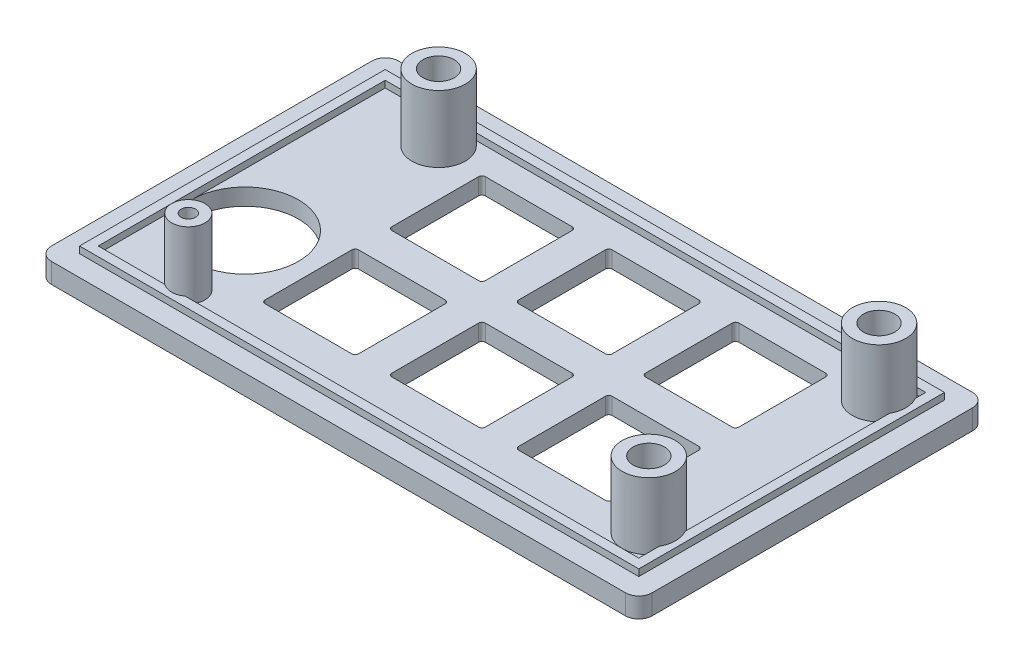
SolidWorks part; units mm, degrees
ref_plane "Front Plane" through (0, 0, 0) normal (0, 0, 1) x (1, 0, 0)
ref_plane "Top Plane" through (0, 0, 0) normal (0, 1, 0) x (1, 0, 0)
ref_plane "Right Plane" through (0, 0, 0) normal (1, 0, 0) x (0, 0, -1)
sketch "Sketch3" plane through (0, 0, 0) normal (0, 1, 0) x (1, 0, 0)
  line L0 (-45, 26) -> (45, 26)
  line L1 (-45, 26) -> (-45, -26)
  line L2 (-45, -26) -> (45, -26)
  line L3 (45, 26) -> (45, -26)
  dimension "D1" = 90
  dimension "D2" = 52
  dimension "D3" = 45
  dimension "D4" = 26
extrude "Boss-Extrude2" add sketch "Sketch3" along normal blind 3
fillet "Fillet2" radius 2 4 edges at (-45, 1.5, 26) (45, 1.5, 26) (45, 1.5, -26) (-45, 1.5, -26)
sketch "Sketch4" plane through (0, 0, 0) normal (0, 1, 0) x (1, 0, 0)
  line L1 (-41.5, 22.5) -> (41.5, 22.5)
  line L2 (-41.5, 22.5) -> (-41.5, -22.5)
  line L3 (-41.5, -22.5) -> (41.5, -22.5)
  line L4 (41.5, 22.5) -> (41.5, -22.5)
  dimension "D1" = 83
  dimension "D2" = 45
  dimension "D3" = 41.5
  dimension "D4" = 22.5
sketch "Sketch5" plane through (0, 0, 0) normal (0, 1, 0) x (1, 0, 0)
  line L8 (16.5, 17.5) -> (29.5, 17.5)
  line L9 (16.5, 3.5) -> (29.5, 3.5)
  line L10 (16, 17) -> (16, 4)
  line L11 (30, 17) -> (30, 4)
  line L25 (41.5, 22.5) -> (41.5, -22.5) construction
  line L26 (-2.5, 17.5) -> (10.5, 17.5)
  line L27 (-2.5, 3.5) -> (10.5, 3.5)
  line L28 (-3, 17) -> (-3, 4)
  line L29 (11, 17) -> (11, 4)
  line L30 (-21.5, 17.5) -> (-8.5, 17.5)
  line L31 (-21.5, 3.5) -> (-8.5, 3.5)
  line L32 (-22, 17) -> (-22, 4)
  line L33 (-8, 17) -> (-8, 4)
  line L34 (16.5, -1.5) -> (29.5, -1.5)
  line L35 (16.5, -15.5) -> (29.5, -15.5)
  line L36 (16, -2) -> (16, -15)
  line L37 (30, -2) -> (30, -15)
  line L38 (-2.5, -1.5) -> (10.5, -1.5)
  line L39 (-2.5, -15.5) -> (10.5, -15.5)
  line L40 (-3, -2) -> (-3, -15)
  line L41 (11, -2) -> (11, -15)
  line L42 (-21.5, -1.5) -> (-8.5, -1.5)
  line L43 (-21.5, -15.5) -> (-8.5, -15.5)
  line L44 (-22, -2) -> (-22, -15)
  line L45 (-8, -2) -> (-8, -15)
  line L46 (-41.5, 22.5) -> (-41.5, -22.5) construction
  line L47 (-41.5, -22.5) -> (41.5, -22.5) construction
  line L48 (-41.5, 22.5) -> (41.5, 22.5) construction
  arc A8 (16.5, 17.5) -> (16, 17) centre (16.5, 17) ccw
  arc A9 (30, 17) -> (29.5, 17.5) centre (29.5, 17) ccw
  arc A10 (16, 4) -> (16.5, 3.5) centre (16.5, 4) ccw
  arc A11 (29.5, 3.5) -> (30, 4) centre (29.5, 4) ccw
  arc A12 (-2.5, 17.5) -> (-3, 17) centre (-2.5, 17) ccw
  arc A13 (11, 17) -> (10.5, 17.5) centre (10.5, 17) ccw
  arc A14 (-3, 4) -> (-2.5, 3.5) centre (-2.5, 4) ccw
  arc A15 (10.5, 3.5) -> (11, 4) centre (10.5, 4) ccw
  arc A16 (-21.5, 17.5) -> (-22, 17) centre (-21.5, 17) ccw
  arc A17 (-8, 17) -> (-8.5, 17.5) centre (-8.5, 17) ccw
  arc A18 (-22, 4) -> (-21.5, 3.5) centre (-21.5, 4) ccw
  arc A19 (-8.5, 3.5) -> (-8, 4) centre (-8.5, 4) ccw
  arc A20 (16.5, -1.5) -> (16, -2) centre (16.5, -2) ccw
  arc A21 (30, -2) -> (29.5, -1.5) centre (29.5, -2) ccw
  arc A22 (16, -15) -> (16.5, -15.5) centre (16.5, -15) ccw
  arc A23 (29.5, -15.5) -> (30, -15) centre (29.5, -15) ccw
  arc A24 (-2.5, -1.5) -> (-3, -2) centre (-2.5, -2) ccw
  arc A25 (11, -2) -> (10.5, -1.5) centre (10.5, -2) ccw
  arc A26 (-3, -15) -> (-2.5, -15.5) centre (-2.5, -15) ccw
  arc A27 (10.5, -15.5) -> (11, -15) centre (10.5, -15) ccw
  arc A28 (-21.5, -1.5) -> (-22, -2) centre (-21.5, -2) ccw
  arc A29 (-8, -2) -> (-8.5, -1.5) centre (-8.5, -2) ccw
  arc A30 (-22, -15) -> (-21.5, -15.5) centre (-21.5, -15) ccw
  arc A31 (-8.5, -15.5) -> (-8, -15) centre (-8.5, -15) ccw
  circle A32 centre (-32.5, -7.5) radius 8
  dimension "D3" = 0.5
  dimension "D12" = 2
  dimension "D11" = 5
  dimension "D16" = 9
  dimension "D14" = 16
  dimension "D1" = 13
  dimension "D2" = 13
  dimension "D4" = 5
  dimension "D5" = 11.5
  dimension "D6" = 0.5
  dimension "D7" = 0.5
  dimension "D8" = 0.5
  dimension "D9" = 0.5
  dimension "D10" = 3
  dimension "D13" = 5
  dimension "D15" = 15
extrude "Cut-Extrude1" cut sketch "Sketch5" along normal through all both and the other way through all
sketch "Sketch7" plane through (0, 0, 0) normal (0, 1, 0) x (1, 0, 0)
  line L0 (-41.5, 22.5) -> (41.5, 22.5) construction
  line L1 (-41.5, 22.5) -> (-41.5, -22.5) construction
  line L2 (41.5, 22.5) -> (41.5, -22.5) construction
  line L3 (-41.5, -22.5) -> (41.5, -22.5) construction
  circle A0 centre (37, 18) radius 4
  circle A1 centre (-29, 18) radius 4
  circle A3 centre (37, -16.5) radius 4
  dimension "D1" = 8
  dimension "D2" = 4.5
  dimension "D3" = 12.5
  dimension "D4" = 4.5
  dimension "D5" = 6
extrude "Boss-Extrude3" add sketch "Sketch7" along normal blind 10 from surface starting at face at (23, 3, 8.5)
sketch "Sketch8" plane through (0, 0, 0) normal (0, 1, 0) x (1, 0, 0)
  circle A0 centre (-29, 18) radius 2.35
  circle A1 centre (37, 18) radius 2.35
  circle A2 centre (37, -16.5) radius 2.35
  dimension "D1" = 4.7
extrude "Cut-Extrude2" cut sketch "Sketch8" against normal blind 4 and the other way through all from surface starting at face at (-29, 13, -14)
sketch "Sketch10" plane through (0, 0, 0) normal (0, 1, 0) x (1, 0, 0)
  line L4 (40.5, 21.5) -> (-40.5, 21.5)
  line L5 (-40.5, 21.5) -> (-40.5, -21.5)
  line L6 (-40.5, -21.5) -> (40.5, -21.5)
  line L7 (40.5, -21.5) -> (40.5, 21.5)
  line L8 (41.9, 22.9) -> (-41.9, 22.9)
  line L9 (41.9, -22.9) -> (41.9, 22.9)
  line L10 (-41.9, -22.9) -> (41.9, -22.9)
  line L11 (-41.9, 22.9) -> (-41.9, -22.9)
  line L12 (41.9, 22.9) -> (-41.9, 22.9)
  line L13 (41.9, -22.9) -> (41.9, 22.9)
  line L14 (-41.9, -22.9) -> (41.9, -22.9)
  line L15 (-41.9, 22.9) -> (-41.9, -22.9)
  dimension "D1" = 0.4
  dimension "D2" = 1.4
extrude "Boss-Extrude4" add sketch "Sketch10" along normal blind 1 from surface starting at face at (37, 3, 20.5)
sketch "Sketch11" plane through (0, 0, 0) normal (0, 1, 0) x (1, 0, 0)
  line L0 (-41.5, -22.5) -> (41.5, -22.5) construction
  circle A0 centre (-29, -19.5) radius 2.5
  dimension "D2" = 5
  dimension "D1" = 3
extrude "Boss-Extrude5" add sketch "Sketch11" along normal blind 10 from surface starting at face at (-2.3679, 3, 0.7315)
sketch "Sketch12" plane through (0, 0, 0) normal (0, 1, 0) x (1, 0, 0)
  circle A0 centre (-29, -19.5) radius 1.075
  dimension "D1" = 2.15
extrude "Cut-Extrude3" cut sketch "Sketch12" against normal blind 10 from surface starting at face at (-29, 13, 22)
extrude "Cut-Extrude4" cut sketch "Sketch4" along normal blind 0.5
sketch "Sketch14" plane through (0, 0, 0) normal (0, 1, 0) x (1, 0, 0)
  line L2 (41.5, 22.5) -> (-41.5, 22.5) construction
  line L3 (-41.5, 22.5) -> (-41.5, -22.5) construction
  text T0 "CADpad\r\n  v1\r\n" font "Century Gothic" height 2.6
  dimension "D1" = 9
  dimension "D2" = 18.5
extrude "Boss-Extrude6" add sketch "Sketch14" along normal blind 0.5
